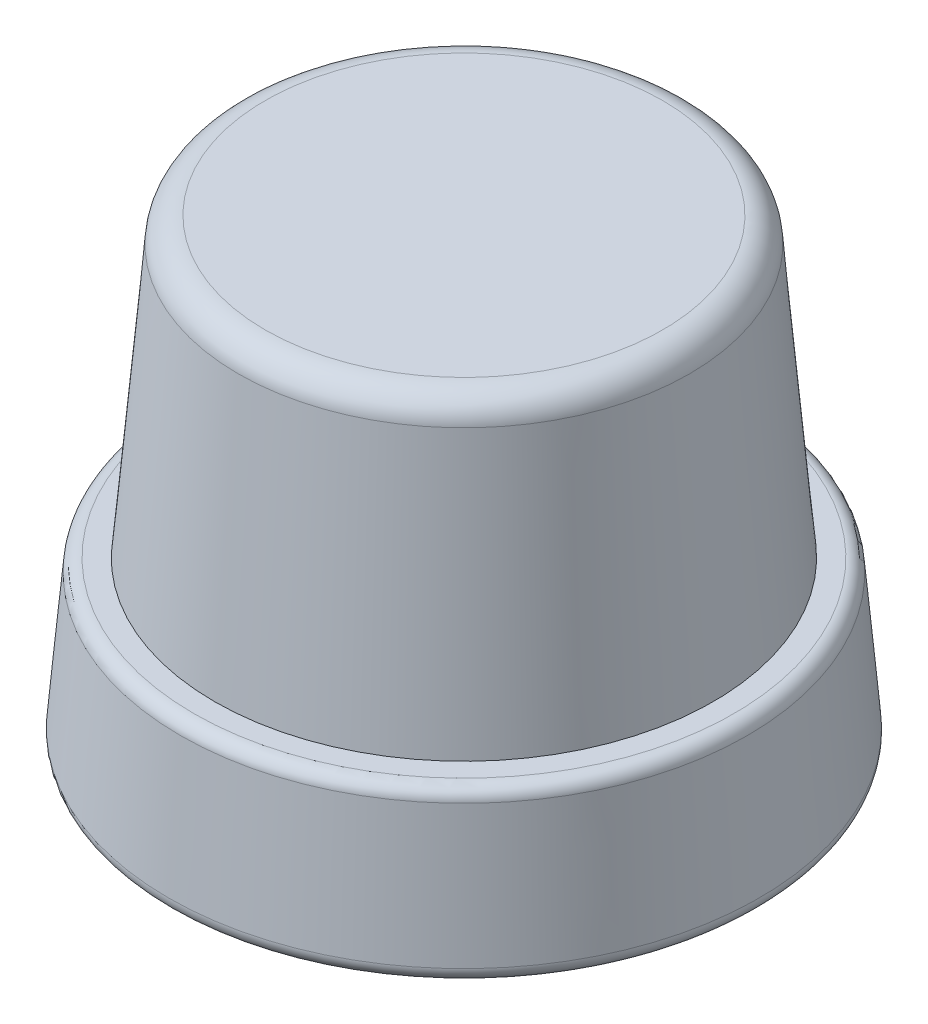
SolidWorks part; units mm, degrees
ref_plane "Front" through (0, 0, 0) normal (0, 0, 1) x (1, 0, 0)
ref_plane "Top" through (0, 0, 0) normal (0, 1, 0) x (1, 0, 0)
ref_plane "Right" through (0, 0, 0) normal (1, 0, 0) x (0, 0, -1)
sketch "Sketch1" plane through (0, 0, 0) normal (0, 1, 0) x (1, 0, 0)
  circle A0 centre (0, 0) radius 11
  dimension "D1" = 22
extrude "Boss-Extrude1" add sketch "Sketch1" along normal blind 6 draft 5
sketch "Sketch2" plane through (0, 6, 0) normal (0, 1, 0) x (1, 0, 0)
  circle A0 centre (0, 0) radius 9.25
  dimension "D1" = 18.5
extrude "Boss-Extrude2" add sketch "Sketch2" along normal blind 11 draft 5
sketch "Sketch3" plane through (0, 0, 0) normal (0, -1, 0) x (1, 0, 0)
  circle A1 centre (0, 0) radius 3.05
  dimension "D1" = 6.1
extrude "Cut-Extrude1" cut sketch "Sketch3" against normal blind 8
sketch "Sketch4" plane through (0, 0, 0) normal (0, -1, 0) x (1, 0, 0)
  line L1 (-2.4384, -7.2384) -> (2.4384, -7.2384)
  line L2 (-2.4384, -7.2384) -> (-2.4384, -3.6824)
  line L3 (-2.4384, -3.6824) -> (2.4384, -3.6824)
  line L4 (2.4384, -7.2384) -> (2.4384, -3.6824)
  point P4 (0, -3.6824)
  point P6 (2.4384, -5.4604)
  dimension "D1" = 1.778
  dimension "D2" = 4.8768
extrude "Cut-Extrude2" [suppressed] cut sketch "Sketch4" against normal blind 6.35
sketch "Sketch5" [suppressed] plane through (0, 0, -3.6824) normal (0, 0, -1) x (-1, 0, 0)
  line L5 (0, 0) -> (0, 6.35) construction
  line L6 (-2.4384, 0) -> (2.4384, 0) construction
  line L7 (-2.4384, 6.35) -> (2.4384, 6.35) construction
  circle A1 centre (0, 3.175) radius 1.2065
  dimension "D1" = 2.413
extrude "Cut-Extrude3" [suppressed] cut sketch "Sketch5" against normal blind 4 contours A1
sketch "Sketch6" [suppressed] plane through (0, 0, -7.2384) normal (0, 0, 1) x (1, 0, 0)
  line L0 (0, -0.0882) -> (0, 6.4715) construction
  circle A0 centre (0, 3.1917) radius 1.143
  dimension "D1" = 2.286
extrude "Cut-Extrude4" [suppressed] cut sketch "Sketch6" against normal blind 4
sketch "Sketch7" [suppressed] plane through (0, 0, -7.2384) normal (0, 0, 1) x (1, 0, 0)
  circle A0 centre (0, 3.1917) radius 2.159
  dimension "D1" = 4.318
extrude "Cut-Extrude5" [suppressed] cut sketch "Sketch7" against normal blind 4 from offset 1.5 offset against normal yes
fillet "Fillet1" radius 1 1 edges at (0, 17, 8.2876)
fillet "Fillet2" radius 0.5 1 edges at (0, 6, 10.4751)
fillet "Fillet3" radius 0.5 1 edges at (0, 0, 11)
